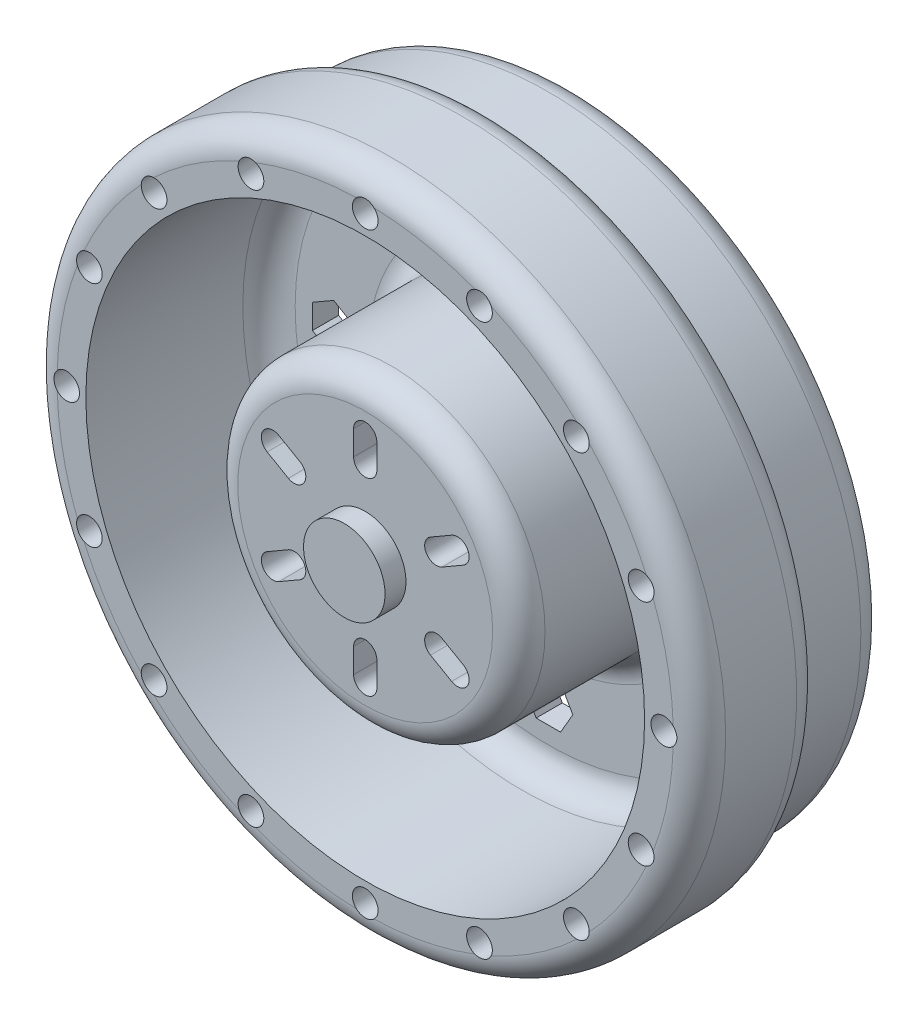
SolidWorks part; units mm, degrees
ref_plane "Front Plane" through (0, 0, 0) normal (0, 0, 1) x (1, 0, 0)
ref_plane "Top Plane" through (0, 0, 0) normal (0, 1, 0) x (1, 0, 0)
ref_plane "Right Plane" through (0, 0, 0) normal (1, 0, 0) x (0, 0, -1)
sketch "Sketch1" plane through (0, 0, 0) normal (0, 0, 1) x (1, 0, 0)
  circle A0 centre (0, 0) radius 64.8986
extrude "Boss-Extrude1" add sketch "Sketch1" along normal blind 40.64
sketch "Sketch2" plane through (0, 0, 40.64) normal (0, 0, 1) x (1, 0, 0)
  circle A0 centre (0, 0) radius 54.2432
extrude "Cut-Extrude1" cut sketch "Sketch2" against normal blind 35.56
sketch "Sketch4" plane through (0, 0, 40.64) normal (0, 0, 1) x (1, 0, 0)
  circle A0 centre (0, 57.9724) radius 2.4964
  circle A1 centre (22.1851, 53.5596) radius 2.4964
  circle A2 centre (40.9927, 40.9927) radius 2.4964
  circle A3 centre (53.5596, 22.1851) radius 2.4964
  circle A4 centre (57.9724, 0) radius 2.4964
  circle A5 centre (53.5596, -22.1851) radius 2.4964
  circle A6 centre (40.9927, -40.9927) radius 2.4964
  circle A7 centre (22.1851, -53.5596) radius 2.4964
  circle A8 centre (0, -57.9724) radius 2.4964
  circle A9 centre (-22.1851, -53.5596) radius 2.4964
  circle A10 centre (-40.9927, -40.9927) radius 2.4964
  circle A11 centre (-53.5596, -22.1851) radius 2.4964
  circle A12 centre (-57.9724, 0) radius 2.4964
  circle A13 centre (-53.5596, 22.1851) radius 2.4964
  circle A14 centre (-40.9927, 40.9927) radius 2.4964
  circle A15 centre (-22.1851, 53.5596) radius 2.4964
  point P34 (0, 0)
  dimension "D1" = 16
extrude "Cut-Extrude3" cut sketch "Sketch4" against normal blind 17.78
sketch "Sketch5" plane through (0, 0, 5.08) normal (0, 0, 1) x (1, 0, 0)
  circle A0 centre (0, 0) radius 29.8338
extrude "Boss-Extrude2" add sketch "Sketch5" along normal blind 35.56
sketch "Sketch6" plane through (0, 0, 5.08) normal (0, 0, 1) x (1, 0, 0)
  line L0 (26.1299, 32.8421) -> (24.9014, 28.2576)
  line L1 (-4.7463, 41.6995) -> (-2.3731, 37.5891)
  line L2 (-2.3731, 37.5891) -> (2.3731, 37.5891)
  line L3 (2.3731, 37.5891) -> (4.7463, 41.6995)
  line L4 (4.7463, 41.6995) -> (2.3731, 45.8099)
  line L5 (2.3731, 45.8099) -> (-2.3731, 45.8099)
  line L6 (-2.3731, 45.8099) -> (-4.7463, 41.6995)
  line L7 (24.9014, 28.2576) -> (28.2576, 24.9014)
  line L8 (28.2576, 24.9014) -> (32.8421, 26.1299)
  line L9 (32.8421, 26.1299) -> (34.0705, 30.7144)
  line L10 (34.0705, 30.7144) -> (30.7144, 34.0705)
  line L11 (30.7144, 34.0705) -> (26.1299, 32.8421)
  line L12 (41.6995, 4.7463) -> (37.5891, 2.3731)
  line L13 (37.5891, 2.3731) -> (37.5891, -2.3731)
  line L14 (37.5891, -2.3731) -> (41.6995, -4.7463)
  line L15 (41.6995, -4.7463) -> (45.8099, -2.3731)
  line L16 (45.8099, -2.3731) -> (45.8099, 2.3731)
  line L17 (45.8099, 2.3731) -> (41.6995, 4.7463)
  line L18 (32.8421, -26.1299) -> (28.2576, -24.9014)
  line L19 (28.2576, -24.9014) -> (24.9014, -28.2576)
  line L20 (24.9014, -28.2576) -> (26.1299, -32.8421)
  line L21 (26.1299, -32.8421) -> (30.7144, -34.0705)
  line L22 (30.7144, -34.0705) -> (34.0705, -30.7144)
  line L23 (34.0705, -30.7144) -> (32.8421, -26.1299)
  line L24 (4.7463, -41.6995) -> (2.3731, -37.5891)
  line L25 (2.3731, -37.5891) -> (-2.3731, -37.5891)
  line L26 (-2.3731, -37.5891) -> (-4.7463, -41.6995)
  line L27 (-4.7463, -41.6995) -> (-2.3731, -45.8099)
  line L28 (-2.3731, -45.8099) -> (2.3731, -45.8099)
  line L29 (2.3731, -45.8099) -> (4.7463, -41.6995)
  line L30 (-26.1299, -32.8421) -> (-24.9014, -28.2576)
  line L31 (-24.9014, -28.2576) -> (-28.2576, -24.9014)
  line L32 (-28.2576, -24.9014) -> (-32.8421, -26.1299)
  line L33 (-32.8421, -26.1299) -> (-34.0705, -30.7144)
  line L34 (-34.0705, -30.7144) -> (-30.7144, -34.0705)
  line L35 (-30.7144, -34.0705) -> (-26.1299, -32.8421)
  line L36 (-41.6995, -4.7463) -> (-37.5891, -2.3731)
  line L37 (-37.5891, -2.3731) -> (-37.5891, 2.3731)
  line L38 (-37.5891, 2.3731) -> (-41.6995, 4.7463)
  line L39 (-41.6995, 4.7463) -> (-45.8099, 2.3731)
  line L40 (-45.8099, 2.3731) -> (-45.8099, -2.3731)
  line L41 (-45.8099, -2.3731) -> (-41.6995, -4.7463)
  line L42 (-32.8421, 26.1299) -> (-28.2576, 24.9014)
  line L43 (-28.2576, 24.9014) -> (-24.9014, 28.2576)
  line L44 (-24.9014, 28.2576) -> (-26.1299, 32.8421)
  line L45 (-26.1299, 32.8421) -> (-30.7144, 34.0705)
  line L46 (-30.7144, 34.0705) -> (-34.0705, 30.7144)
  line L47 (-34.0705, 30.7144) -> (-32.8421, 26.1299)
  circle A0 centre (0, 41.6995) radius 4.1104 construction
  point P52 (0, 0)
  dimension "D1" = 8
extrude "Cut-Extrude4" cut sketch "Sketch6" against normal blind 35.56
sketch "Sketch7" plane through (0, 0, 0) normal (0, 0, -1) x (-1, 0, 0)
  circle A0 centre (0, 0) radius 19.4372
extrude "Cut-Extrude5" cut sketch "Sketch7" against normal blind 16.764
sketch "Sketch8" plane through (0, 0, 0) normal (0, 0, -1) x (-1, 0, 0)
  circle A0 centre (0, 0) radius 64.8986
  circle A1 centre (0, 0) radius 60.6728
extrude "Cut-Extrude8" cut sketch "Sketch8" against normal blind 16.764
sketch "Sketch10" plane through (0, 0, 40.64) normal (0, 0, 1) x (1, 0, 0)
  line L0 (0, 20.6802) -> (0, 15.9339) construction
  line L1 (2.2601, 20.6802) -> (2.2601, 15.9339)
  line L2 (-2.2601, 20.6802) -> (-2.2601, 15.9339)
  line L3 (17.9096, 10.3401) -> (13.7992, 7.967) construction
  line L4 (19.0397, 8.3828) -> (14.9293, 6.0096)
  line L5 (16.7795, 12.2974) -> (12.6691, 9.9243)
  line L6 (17.9096, -10.3401) -> (13.7992, -7.967) construction
  line L7 (16.7795, -12.2974) -> (12.6691, -9.9243)
  line L8 (19.0397, -8.3828) -> (14.9293, -6.0096)
  line L9 (0, -20.6802) -> (0, -15.9339) construction
  line L10 (-2.2601, -20.6802) -> (-2.2601, -15.9339)
  line L11 (2.2601, -20.6802) -> (2.2601, -15.9339)
  line L12 (-17.9096, -10.3401) -> (-13.7992, -7.967) construction
  line L13 (-19.0397, -8.3828) -> (-14.9293, -6.0096)
  line L14 (-16.7795, -12.2974) -> (-12.6691, -9.9243)
  line L15 (-17.9096, 10.3401) -> (-13.7992, 7.967) construction
  line L16 (-16.7795, 12.2974) -> (-12.6691, 9.9243)
  line L17 (-19.0397, 8.3828) -> (-14.9293, 6.0096)
  arc A0 (2.2601, 20.6802) -> (-2.2601, 20.6802) centre (0, 20.6802) ccw
  arc A1 (-2.2601, 15.9339) -> (2.2601, 15.9339) centre (0, 15.9339) ccw
  arc A2 (19.0397, 8.3828) -> (16.7795, 12.2974) centre (17.9096, 10.3401) ccw
  arc A3 (12.6691, 9.9243) -> (14.9293, 6.0096) centre (13.7992, 7.967) ccw
  arc A4 (16.7795, -12.2974) -> (19.0397, -8.3828) centre (17.9096, -10.3401) ccw
  arc A5 (14.9293, -6.0096) -> (12.6691, -9.9243) centre (13.7992, -7.967) ccw
  arc A6 (-2.2601, -20.6802) -> (2.2601, -20.6802) centre (0, -20.6802) ccw
  arc A7 (2.2601, -15.9339) -> (-2.2601, -15.9339) centre (0, -15.9339) ccw
  arc A8 (-19.0397, -8.3828) -> (-16.7795, -12.2974) centre (-17.9096, -10.3401) ccw
  arc A9 (-12.6691, -9.9243) -> (-14.9293, -6.0096) centre (-13.7992, -7.967) ccw
  arc A10 (-16.7795, 12.2974) -> (-19.0397, 8.3828) centre (-17.9096, 10.3401) ccw
  arc A11 (-14.9293, 6.0096) -> (-12.6691, 9.9243) centre (-13.7992, 7.967) ccw
  point P3 (0, 18.3071)
  point P12 (15.8544, 9.1535)
  point P19 (15.8544, -9.1535)
  point P26 (0, -18.3071)
  point P33 (-15.8544, -9.1535)
  point P40 (-15.8544, 9.1535)
  point P45 (0, 0)
  dimension "D1" = 6
extrude "Cut-Extrude9" cut sketch "Sketch10" against normal blind 16.764
fillet "Fillet1" radius 5.08 3 edges at (29.8338, 0, 40.64) (64.8986, 0, 40.64) (-64.8986, 0, 16.764)
fillet "Fillet2" radius 5.08 5 edges at (-19.4372, 0, 16.764) (29.8338, 0, 5.08) (54.2432, 0, 5.08) (-19.4372, 0, 0) (-60.6728, 0, 0)
sketch "Sketch11" plane through (0, 0, 40.64) normal (0, 0, 1) x (1, 0, 0)
  circle A0 centre (0, 0) radius 7.9105
extrude "Boss-Extrude3" add sketch "Sketch11" along normal blind 4.064
